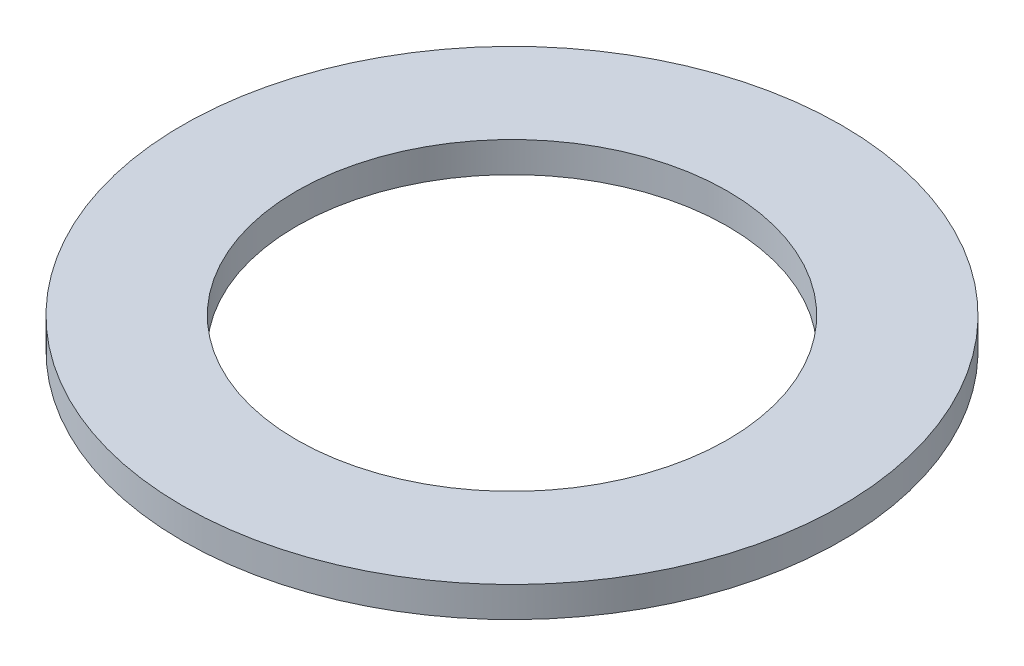
SolidWorks part; units mm, degrees
ref_plane "Front Plane" through (0, 0, 0) normal (0, 0, 1) x (1, 0, 0)
ref_plane "Top Plane" through (0, 0, 0) normal (0, 1, 0) x (1, 0, 0)
ref_plane "Right Plane" through (0, 0, 0) normal (1, 0, 0) x (0, 0, -1)
sketch "Sketch1" plane through (0, 0, 0) normal (0, 1, 0) x (1, 0, 0)
  circle A0 centre (0, 0) radius 65
  dimension "FLANGE_OD" = 130
extrude "Boss-Extrude1" add sketch "Sketch1" along normal blind 6
sketch "Sketch2" plane through (0, 0, 0) normal (0, 1, 0) x (1, 0, 0)
  circle A0 centre (0, 0) radius 42.5
  dimension "BORE_D" = 85
extrude "Cut-Extrude1" cut sketch "Sketch2" along normal through all
sketch "Sketch3" plane through (0, 6, 0) normal (0, 1, 0) x (1, 0, 0)
  circle A0 centre (0, 0) radius 29.3846 construction
  circle A1 centre (-29.3846, 0) radius 2.2798
  dimension "BOLT_D" = 4.5596
  dimension "BOLT_PCD" = 58.7692
extrude "Cut-Extrude2" cut sketch "Sketch3" against normal blind 4.094 rebuild error yes
pattern_circular "CirPattern1" count 3 over 360 rebuild error yes
